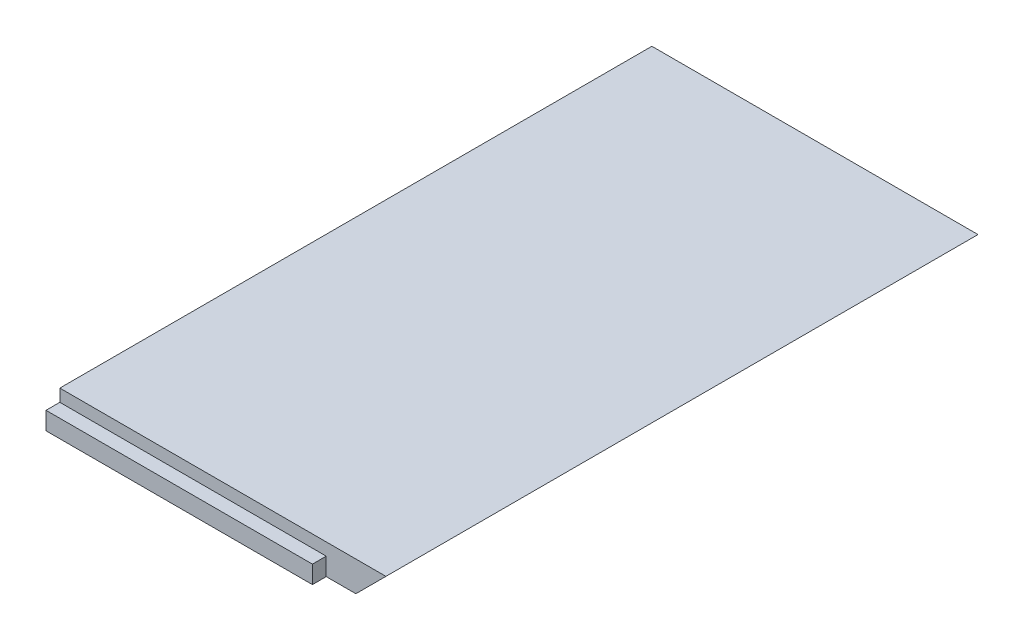
SolidWorks part; units mm, degrees
ref_plane "Plan de face" through (0, 0, 0) normal (0, 0, 1) x (1, 0, 0)
ref_plane "Plan de dessus" through (0, 0, 0) normal (0, 1, 0) x (1, 0, 0)
ref_plane "Plan de droite" through (0, 0, 0) normal (1, 0, 0) x (0, 0, -1)
sketch "Esquisse1" plane through (0, 0, 0) normal (0, 0, 1) x (1, 0, 0)
  line L0 (-465.25, 185.3139) -> (0, 185.3139) construction
  line L1 (-300, 185.3139) -> (-465.25, 185.3139)
  line L2 (-300, 185.3139) -> (-300, 170.0639)
  line L3 (-300, 170.0639) -> (-465.25, 170.0639)
  line L4 (-465.25, 185.3139) -> (-465.25, 170.0639)
  line L5 (-465.25, -3.9361) -> (-465.25, 170.0639) construction
  line L6 (0, 185.3139) -> (0, -20.1861) construction
  dimension "D1" = 15.25
  dimension "D2" = 300
extrude "Boss.-Extru.1" add sketch "Esquisse1" along normal up to surface (300 mm away)
sketch "Esquisse3" plane through (-465.25, 0, 0) normal (-1, 0, 0) x (0, 0, 1)
  line L0 (300, 185.3139) -> (300, 170.0639) construction
  line L1 (300, 179.0639) -> (307, 179.0639)
  line L2 (300, 179.0639) -> (300, 170.0639)
  line L3 (300, 170.0639) -> (307, 170.0639)
  line L4 (307, 179.0639) -> (307, 170.0639)
  dimension "D1" = 9
  dimension "D2" = 7
extrude "Boss.-Extru.4" add sketch "Esquisse3" against normal up to surface (165.25 mm away) up to face at (-300, 177.6889, 150)
sketch "Esquisse2" plane through (0, 0, 300) normal (0, 0, 1) x (1, 0, 0)
  line L0 (-300, 185.3139) -> (-315.25, 170.0639)
  line L1 (-465.25, 170.0639) -> (-300, 170.0639) construction
  line L2 (-315.25, 170.0639) -> (-300, 170.0639)
  line L3 (-300, 170.0639) -> (-300, 185.3139)
extrude "Enlèv. mat.-Extru.2" cut sketch "Esquisse2" against normal up to next and the other way up to next
sketch "Esquisse4" plane through (0, 0, 307) normal (0, 0, 1) x (1, 0, 0)
  line L0 (-306.25, 179.0639) -> (-465.25, 179.0639) construction
  line L1 (-330.25, 179.0639) -> (-306.25, 179.0639)
  line L2 (-330.25, 179.0639) -> (-330.25, 170.0639)
  line L3 (-330.25, 170.0639) -> (-306.25, 170.0639)
  line L4 (-306.25, 179.0639) -> (-306.25, 170.0639)
  line L5 (-315.25, 170.0639) -> (-465.25, 170.0639) construction
  line L6 (-465.25, 170.0639) -> (-465.25, 179.0639) construction
  dimension "D1" = 135
extrude "Enlèv. mat.-Extru.3" cut sketch "Esquisse4" against normal up to surface (7 mm away) up to face at (-384.1875, 182.1889, 300)
